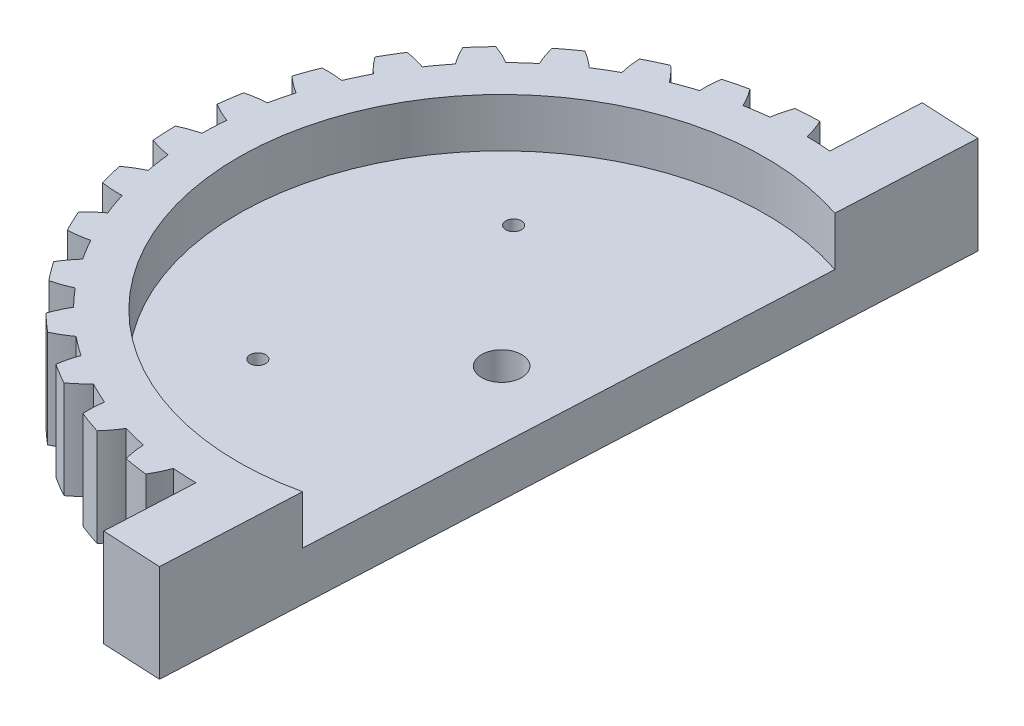
SolidWorks part; units mm, degrees
ref_plane "正面" through (0, 0, 0) normal (0, 0, 1) x (1, 0, 0)
ref_plane "平面" through (0, 0, 0) normal (0, 1, 0) x (1, 0, 0)
ref_plane "右側面" through (0, 0, 0) normal (1, 0, 0) x (0, 0, -1)
sketch "ｽｹｯﾁ1" plane through (0, 0, 0) normal (0, 1, 0) x (1, 0, 0)
  line L0 (0, 0) -> (0, 104.1615) construction
  line L1 (-93.5954, 64) -> (78.777, 64) construction
  line L2 (-63.9379, 40.7285) -> (71.1281, 89.8885) construction
  circle A0 centre (0, 0) radius 64 construction
  circle A1 centre (0, 0) radius 60.1403 construction
  point P7 (0, 64)
  dimension "D1" = 128
  dimension "D2" = 20
sketch "ｽｹｯﾁ2" plane through (0, 0, 0) normal (0, 1, 0) x (1, 0, 0)
  line L0 (-20.5692, 56.5134) -> (0, 64) construction
  line L1 (-14.8381, 58.2811) -> (0.56, 62.2014) construction
  line L2 (-15.8051, 58.0264) -> (0.4905, 62.4649) construction
  line L3 (-16.7677, 57.7555) -> (0.4122, 62.7433) construction
  line L4 (-17.7257, 57.4688) -> (0.3245, 63.0362) construction
  line L5 (-18.6788, 57.1661) -> (0.2269, 63.3434) construction
  line L6 (-19.6267, 56.8476) -> (0.1189, 63.6648) construction
  line L7 (-21.506, 56.1636) -> (-0.1303, 64.3487) construction
  line L8 (-22.4369, 55.7983) -> (-0.2724, 64.7108) construction
  line L9 (-23.3615, 55.4175) -> (-0.4268, 65.0857) construction
  line L10 (-24.2797, 55.0214) -> (-0.594, 65.4734) construction
  line L11 (-25.1912, 54.6101) -> (-0.7745, 65.8733) construction
  line L12 (-26.0957, 54.1837) -> (-0.9688, 66.2852) construction
  line L14 (0, 0) -> (-5.2283, 106.4246) construction
  line L15 (0, 0) -> (0, 104.1615) construction
  circle A0 centre (0, 0) radius 60.1403 construction
  arc A1 (-20.5692, 56.5134) -> (-19.6267, 56.8476) centre (0, 0) cw
  arc A2 (-19.6267, 56.8476) -> (-18.6788, 57.1661) centre (0, 0) cw
  arc A3 (-18.6788, 57.1661) -> (-17.7257, 57.4688) centre (0, 0) cw
  arc A4 (-17.7257, 57.4688) -> (-16.7677, 57.7555) centre (0, 0) cw
  arc A5 (-16.7677, 57.7555) -> (-15.8051, 58.0264) centre (0, 0) cw
  arc A6 (-15.8051, 58.0264) -> (-14.8381, 58.2811) centre (0, 0) cw
  arc A7 (-20.5692, 56.5134) -> (-21.506, 56.1636) centre (0, 0) ccw
  arc A8 (-21.506, 56.1636) -> (-22.4369, 55.7983) centre (0, 0) ccw
  arc A9 (-22.4369, 55.7983) -> (-23.3615, 55.4175) centre (0, 0) ccw
  arc A10 (-23.3615, 55.4175) -> (-24.2797, 55.0214) centre (0, 0) ccw
  arc A11 (-24.2797, 55.0214) -> (-25.1912, 54.6101) centre (0, 0) ccw
  arc A12 (-25.1912, 54.6101) -> (-26.0957, 54.1837) centre (0, 0) ccw
  arc A13 (-20.5692, 56.5134) -> (0.8963, 60.1336) centre (0, 0) cw
  circle A14 centre (0, 0) radius 66 construction
  circle A16 centre (0, 0) radius 64 construction
  spline S0 degree 3 poles (-0.9688, 66.2852) (-0.8394, 66.0167) (-0.6553, 65.6183) (-0.4279, 65.0913) (-0.2734, 64.7163) (-0.1313, 64.3543) (-0.0009, 64.0056) (0.118, 63.6704) (0.226, 63.349) (0.3237, 63.0417) (0.4114, 62.7488) (0.6791, 61.7983) (0.8527, 60.9277) (0.8963, 60.1336) knots 0 0 0 0 0.138368 0.203693 0.266445 0.326623 0.384229 0.439262 0.491722 0.541609 0.588924 0.633665 1 1 1 1
  spline S1 degree 3 poles (-5.533, 66.061) (-5.6354, 65.7811) (-5.7795, 65.3666) (-5.9542, 64.8198) (-6.0712, 64.4315) (-6.1772, 64.0573) (-6.2727, 63.6974) (-6.3582, 63.3522) (-6.4342, 63.0218) (-6.5013, 62.7064) (-6.5599, 62.4063) (-6.7331, 61.4341) (-6.8206, 60.5507) (-6.7861, 59.7562) knots 0 0 0 0 0.138368 0.203693 0.266445 0.326623 0.384229 0.439262 0.491722 0.541609 0.588924 0.633665 1 1 1 1
  dimension "D1" = 21.8893
  dimension "D3" = 19.8893
  dimension "D4" = 20.8893
  dimension "D5" = 18.8893
  dimension "D6" = 17.8893
  dimension "D7" = 16.8893
  dimension "D8" = 15.8893
  dimension "D9" = 22.8893
  dimension "D10" = 23.8893
  dimension "D11" = 24.8893
  dimension "D12" = 25.8893
  dimension "D13" = 26.8893
  dimension "D14" = 27.8893
  dimension "D15" = 2.813
  dimension "D16" = 2
  dimension "D2" = 1
sketch "ｽｹｯﾁ3" plane through (0, 0, 0) normal (0, 1, 0) x (1, 0, 0)
  arc A1 (0.6104, 61.997) -> (-6.6843, 61.6386) centre (0, 0) ccw
  arc A3 (-0.8309, 65.9948) -> (-5.6417, 65.7584) centre (0, 0) ccw
  spline S2 degree 3 poles (-5.533, 66.061) (-5.6354, 65.7811) (-5.7795, 65.3666) (-5.9542, 64.8198) (-6.0712, 64.4315) (-6.1772, 64.0573) (-6.2727, 63.6974) (-6.3582, 63.3522) (-6.4342, 63.0218) (-6.5013, 62.7064) (-6.5599, 62.4063) (-6.7331, 61.4341) (-6.8206, 60.5507) (-6.7861, 59.7562) knots 0 0 0 0 0.138368 0.203693 0.266445 0.326623 0.384229 0.439262 0.491722 0.541609 0.588924 0.633665 1 1 1 1 construction
  spline S3 degree 3 poles (-0.9688, 66.2852) (-0.8394, 66.0167) (-0.6553, 65.6183) (-0.4279, 65.0913) (-0.2734, 64.7163) (-0.1313, 64.3543) (-0.0009, 64.0056) (0.118, 63.6704) (0.226, 63.349) (0.3237, 63.0417) (0.4114, 62.7488) (0.6791, 61.7983) (0.8527, 60.9277) (0.8963, 60.1336) knots 0 0 0 0 0.138368 0.203693 0.266445 0.326623 0.384229 0.439262 0.491722 0.541609 0.588924 0.633665 1 1 1 1 construction
  spline S4 degree 3 poles (-5.6417, 65.7584) (-5.7052, 65.5784) (-5.8121, 65.2645) (-5.9542, 64.8198) (-6.0712, 64.4315) (-6.1772, 64.0573) (-6.2727, 63.6974) (-6.3582, 63.3522) (-6.4342, 63.0218) (-6.5013, 62.7064) (-6.5599, 62.4063) (-6.6229, 62.0526) (-6.6623, 61.7982) (-6.6843, 61.6386) knots 0 0 0 0 0.134544 0.233721 0.328992 0.420358 0.507816 0.591369 0.671015 0.746755 0.818588 0.886516 1 1 1 1
  spline S5 degree 3 poles (-0.8309, 65.9948) (-0.7501, 65.8218) (-0.6129, 65.5199) (-0.4279, 65.0913) (-0.2734, 64.7163) (-0.1313, 64.3543) (-0.0009, 64.0056) (0.118, 63.6704) (0.226, 63.349) (0.3237, 63.0417) (0.4114, 62.7488) (0.5088, 62.4029) (0.573, 62.1536) (0.6104, 61.997) knots 0 0 0 0 0.134544 0.233721 0.328992 0.420358 0.507816 0.591369 0.671015 0.746755 0.818588 0.886516 1 1 1 1
  point P3 (-5.6417, 65.7584)
  point P4 (-0.8309, 65.9948)
  point P5 (0.6104, 61.997)
  point P6 (-6.6843, 61.6386)
  dimension "D1" = 124
  dimension "D2" = 4
sketch "ｽｹｯﾁ5" plane through (0, 0, 0) normal (0, 1, 0) x (1, 0, 0)
  circle A0 centre (0, 0) radius 62
  dimension "D1" = 124
extrude "ﾎﾞｽ - 押し出し5" add sketch "ｽｹｯﾁ5" along normal blind 20
extrude "ﾎﾞｽ - 押し出し6" add sketch "ｽｹｯﾁ3" along normal blind 20
pattern_circular "円形ﾊﾟﾀｰﾝ3" count 32 over 360 about axis through (0, 20, 0) along (0, 1, 0) of "ﾎﾞｽ - 押し出し6"
sketch "ｽｹｯﾁ8" plane through (0, 20, 0) normal (0, 1, 0) x (1, 0, 0)
  circle A0 centre (0, 0) radius 54
  arc A1 (65.9948, 0.8309) -> (65.7584, 5.6417) centre (0, 0) ccw construction
  dimension "D1" = 12
extrude "ｶｯﾄ - 押し出し3" cut sketch "ｽｹｯﾁ8" against normal offset from surface (10 mm away) 10 up to face at (0, 0, 0)
sketch "ｽｹｯﾁ6" plane through (0, 10, 0) normal (0, 1, 0) x (1, 0, 0)
  line L0 (3.0422, 61.9253) -> (-2449.4393, -49859.4828) construction
  line L1 (-1.6969, 0.0834) -> (-49921.7047, 2452.4961) construction
  circle A0 centre (-23.7432, 26.1966) radius 1.6
  circle A9 centre (-26.1966, -23.7432) radius 1.6
  arc A10 (5.4693, 61.7583) -> (0.6104, 61.997) centre (0, 0) ccw construction
  arc A11 (-5.4693, -61.7583) -> (-0.6104, -61.997) centre (0, 0) ccw construction
  arc A12 (-61.7583, 5.4693) -> (-61.997, 0.6104) centre (0, 0) ccw construction
  point P14 (3.0422, 61.9253)
  point P18 (-3.0422, -61.9253)
  point P24 (-61.9253, 3.0422)
  dimension "D5" = 3.2
  dimension "D1" = 25
  dimension "D2" = 25
sketch "ｽｹｯﾁ7" plane through (0, 20, 0) normal (0, 1, 0) x (1, 0, 0)
  line L12 (-61.3112, 3.012) -> (49878.4616, -2450.3717) construction
  line L14 (11.2948, -65.0264) -> (62.7608, -67.5547)
  line L16 (17.6141, 63.6061) -> (69.0802, 61.0778)
  line L19 (69.0802, 61.0778) -> (62.7608, -67.5547)
  line L20 (17.6141, 63.6061) -> (11.2948, -65.0264)
  circle A3 centre (0, 0) radius 66 construction
  circle A5 centre (0, 0) radius 4.1
  arc A6 (-61.7583, 5.4693) -> (-61.997, 0.6104) centre (0, 0) ccw construction
  arc A7 (61.7583, -5.4693) -> (61.997, -0.6104) centre (0, 0) ccw construction
  point P8 (-61.9253, 3.0422)
  point P12 (61.9253, -3.0422)
  dimension "D3" = 132
  dimension "D4" = 8.2
extrude "ｶｯﾄ - 押し出し2" cut sketch "ｽｹｯﾁ7" against normal through all
sketch "ｽｹｯﾁ9" plane through (0, 0, 0) normal (0, 1, 0) x (1, 0, 0)
  line L0 (6.3548, 79.7843) -> (5.0764, 53.7609)
  line L1 (-1.496, -80.023) -> (10.5291, -80.6137)
  line L2 (0, 0) -> (2453.3837, 49939.7728) construction
  line L3 (-61.9253, 3.0422) -> (49877.8475, -2450.3415) construction
  line L4 (10.5291, -80.6137) -> (11.9018, -52.6721)
  line L5 (18.3799, 79.1935) -> (6.3548, 79.7843)
  line L7 (17.0072, 51.2519) -> (11.9018, -52.6721) construction
  line L8 (17.4126, 59.5046) -> (17.0072, 51.2519) construction
  line L9 (-0.2175, -53.9996) -> (-1.496, -80.023)
  line L10 (17.0072, 51.2519) -> (18.3799, 79.1935)
  arc A0 (5.4693, 61.7583) -> (0.6104, 61.997) centre (0, 0) ccw construction
  arc A1 (-61.7583, 5.4693) -> (-61.997, 0.6104) centre (0, 0) ccw construction
  arc A2 (5.0764, 53.7609) -> (17.0072, 51.2519) centre (0, 0) cw
  arc A3 (-0.2175, -53.9996) -> (11.9018, -52.6721) centre (0, 0) ccw
  arc A4 (17.0072, 51.2519) -> (11.9018, -52.6721) centre (0, 0) ccw construction
  arc A5 (17.0072, 51.2519) -> (11.9018, -52.6721) centre (0, 0) ccw construction
  point P14 (3.0422, 61.9253)
  point P20 (-61.9253, 3.0422)
  point P40 (10.8564, -52.8974)
  point P41 (0, 0)
  point P42 (0, 0)
  point P43 (17.0072, 51.2519)
  dimension "D1" = 80
  dimension "D2" = 80
extrude "ｶｯﾄ - 押し出し5" cut sketch "ｽｹｯﾁ6" against normal through all
extrude "ﾎﾞｽ - 押し出し8" add sketch "ｽｹｯﾁ9" along normal up to surface (20 mm away) up to face at (-33.7678, 20, -1.8228)
equation "\"D3@ｽｹｯﾁ2\"=\"D4@ｽｹｯﾁ2\"-\"D2@ｽｹｯﾁ2\""
equation "\"D4@ｽｹｯﾁ2\"=\"D1@ｽｹｯﾁ2\"-\"D2@ｽｹｯﾁ2\""
equation "\"D5@ｽｹｯﾁ2\"=\"D3@ｽｹｯﾁ2\"-\"D2@ｽｹｯﾁ2\""
equation "\"D6@ｽｹｯﾁ2\"=\"D5@ｽｹｯﾁ2\"-\"D2@ｽｹｯﾁ2\""
equation "\"D7@ｽｹｯﾁ2\"=\"D6@ｽｹｯﾁ2\"-\"D2@ｽｹｯﾁ2\""
equation "\"D8@ｽｹｯﾁ2\"=\"D7@ｽｹｯﾁ2\"-\"D2@ｽｹｯﾁ2\""
equation "\"D9@ｽｹｯﾁ2\"=\"D1@ｽｹｯﾁ2\"+\"D2@ｽｹｯﾁ2\""
equation "\"D10@ｽｹｯﾁ2\"=\"D9@ｽｹｯﾁ2\"+\"D2@ｽｹｯﾁ2\""
equation "\"D11@ｽｹｯﾁ2\"=\"D10@ｽｹｯﾁ2\"+\"D2@ｽｹｯﾁ2\""
equation "\"D12@ｽｹｯﾁ2\"=\"D11@ｽｹｯﾁ2\"+\"D2@ｽｹｯﾁ2\""
equation "\"D13@ｽｹｯﾁ2\"=\"D12@ｽｹｯﾁ2\"+\"D2@ｽｹｯﾁ2\""
equation "\"D14@ｽｹｯﾁ2\"=\"D13@ｽｹｯﾁ2\"+\"D2@ｽｹｯﾁ2\""
equation "\"D15@ｽｹｯﾁ2\"=90/32"
